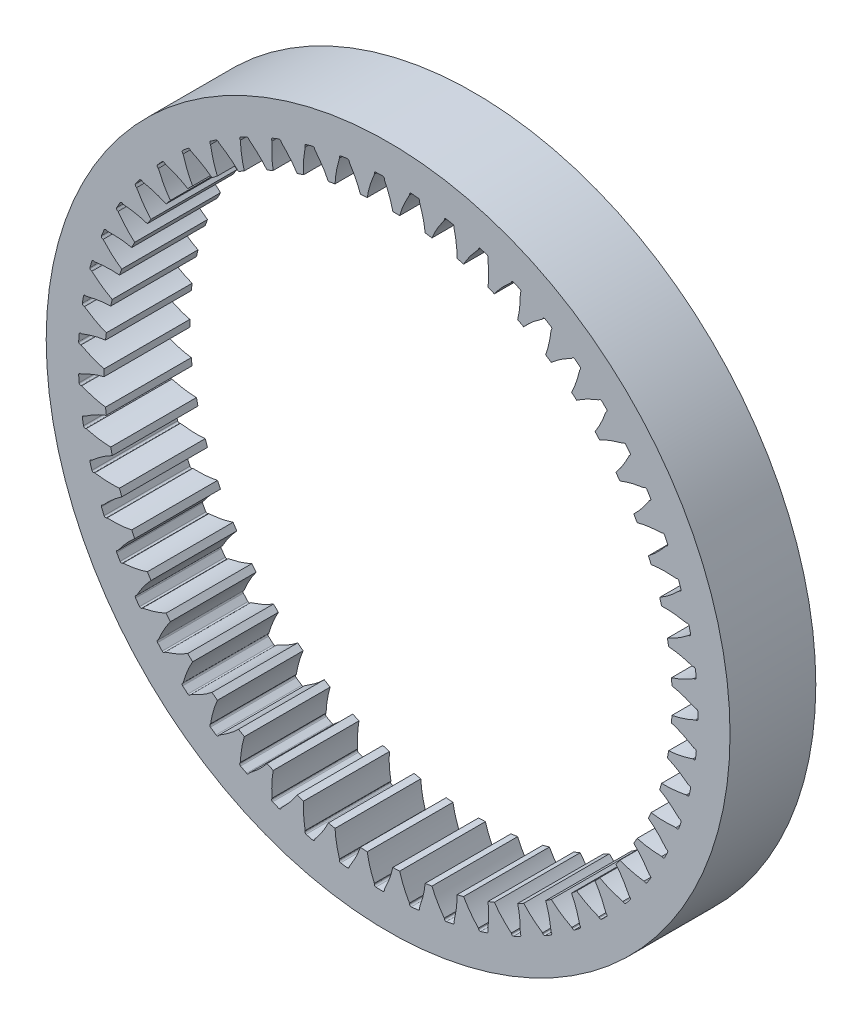
SolidWorks part; units mm, degrees
ref_plane "Front Plane" through (0, 0, 0) normal (0, 0, 1) x (1, 0, 0)
ref_plane "Top Plane" through (0, 0, 0) normal (0, 1, 0) x (1, 0, 0)
ref_plane "Right Plane" through (0, 0, 0) normal (1, 0, 0) x (0, 0, -1)
ref_axis "Gear Axis" through (0, 0, -0.5001) along (0, 0, 1)
sketch "Blank Sketch" plane through (0, 0, 0) normal (0, 0, 1) x (1, 0, 0)
  circle A0 centre (0, 0) radius 39.875
  circle A1 centre (0, 0) radius 33.125
  dimension "Rim" = 79.75
  dimension "Tip" = 66.25
extrude "Blank" add sketch "Blank Sketch" along normal blind 10
sketch "Tooth Space Sketch" plane through (0, 0, 0) normal (0, 0, 1) x (1, 0, 0)
  line L0 (32.4618, 1.5746) -> (31.8376, 1.5443)
  line L1 (32.4618, -1.5746) -> (31.8376, -1.5443)
  line L2 (31.8376, 1.5443) -> (31.8376, -1.5443)
  line L3 (35.839, 0.5828) -> (35.9323, 0.5843)
  line L4 (35.839, -0.5828) -> (35.9323, -0.5843)
  circle A0 centre (0, 0) radius 31.875 construction
  arc A1 (36.1228, 0.3989) -> (35.9323, 0.5843) centre (35.9353, 0.3968) ccw
  arc A2 (35.9323, -0.5843) -> (36.1228, -0.3989) centre (35.9353, -0.3968) ccw
  arc A3 (36.1228, -0.3989) -> (36.1228, 0.3989) centre (0, 0) ccw
  spline S0 degree 4 poles (32.3488, 1.5797) (32.3794, 1.5788) (32.4354, 1.5763) (32.4783, 1.5738) (32.5874, 1.5653) (32.6703, 1.5565) (32.7761, 1.5441) (32.8818, 1.5291) (32.9919, 1.512) (33.099, 1.4933) (33.2074, 1.4728) (33.3145, 1.451) (33.422, 1.4276) (33.5522, 1.3976) (33.7092, 1.3587) (33.8908, 1.3104) (34.0997, 1.2498) (34.3075, 1.1855) (34.5185, 1.1151) (34.721, 1.0444) (34.934, 0.9647) (35.1265, 0.8904) (35.3493, 0.7984) (35.5186, 0.7274) (35.7608, 0.619) (35.8709, 0.5684) (36.0228, 0.4968) (36.0994, 0.4599) (36.1385, 0.4409) (36.1582, 0.4312) knots 0 0 0 0 0 0.027604 0.045881 0.064918 0.092335 0.119753 0.14717 0.174587 0.202005 0.229422 0.256839 0.284256 0.311674 0.363255 0.418089 0.472924 0.527758 0.582593 0.637427 0.692262 0.747097 0.801931 0.856766 0.9116 0.9558 0.9779 1 1 1 1 1 construction
  spline S1 degree 4 poles (32.4618, 1.5746) (32.478, 1.5736) (32.5109, 1.5713) (32.5874, 1.5653) (32.6703, 1.5565) (32.7761, 1.5441) (32.8818, 1.5291) (32.9919, 1.512) (33.099, 1.4933) (33.2074, 1.4728) (33.3145, 1.451) (33.422, 1.4276) (33.5522, 1.3976) (33.7092, 1.3587) (33.8908, 1.3104) (34.0997, 1.2498) (34.3075, 1.1855) (34.5185, 1.1151) (34.721, 1.0444) (34.934, 0.9647) (35.1265, 0.8904) (35.3493, 0.7984) (35.5186, 0.7274) (35.7095, 0.6419) (35.795, 0.6031) (35.839, 0.5828) knots 0.027604 0.027604 0.027604 0.027604 0.027604 0.045881 0.064918 0.092335 0.119753 0.14717 0.174587 0.202005 0.229422 0.256839 0.284256 0.311674 0.363255 0.418089 0.472924 0.527758 0.582593 0.637427 0.692262 0.747097 0.801931 0.856766 0.9116 0.9116 0.9116 0.9116 0.9116
  spline S2 degree 4 poles (32.3488, -1.5797) (32.3794, -1.5788) (32.4354, -1.5763) (32.4783, -1.5738) (32.5874, -1.5653) (32.6703, -1.5565) (32.7761, -1.5441) (32.8818, -1.5291) (32.9919, -1.512) (33.099, -1.4933) (33.2074, -1.4728) (33.3145, -1.451) (33.422, -1.4276) (33.5522, -1.3976) (33.7092, -1.3587) (33.8908, -1.3104) (34.0997, -1.2498) (34.3075, -1.1855) (34.5185, -1.1151) (34.721, -1.0444) (34.934, -0.9647) (35.1265, -0.8904) (35.3493, -0.7984) (35.5186, -0.7274) (35.7608, -0.619) (35.8709, -0.5684) (36.0228, -0.4968) (36.0994, -0.4599) (36.1385, -0.4409) (36.1582, -0.4312) knots 0 0 0 0 0 0.027604 0.045881 0.064918 0.092335 0.119753 0.14717 0.174587 0.202005 0.229422 0.256839 0.284256 0.311674 0.363255 0.418089 0.472924 0.527758 0.582593 0.637427 0.692262 0.747097 0.801931 0.856766 0.9116 0.9558 0.9779 1 1 1 1 1 construction
  spline S3 degree 4 poles (32.4618, -1.5746) (32.478, -1.5736) (32.5109, -1.5713) (32.5874, -1.5653) (32.6703, -1.5565) (32.7761, -1.5441) (32.8818, -1.5291) (32.9919, -1.512) (33.099, -1.4933) (33.2074, -1.4728) (33.3145, -1.451) (33.422, -1.4276) (33.5522, -1.3976) (33.7092, -1.3587) (33.8908, -1.3104) (34.0997, -1.2498) (34.3075, -1.1855) (34.5185, -1.1151) (34.721, -1.0444) (34.934, -0.9647) (35.1265, -0.8904) (35.3493, -0.7984) (35.5186, -0.7274) (35.7095, -0.6419) (35.795, -0.6031) (35.839, -0.5828) knots 0.027604 0.027604 0.027604 0.027604 0.027604 0.045881 0.064918 0.092335 0.119753 0.14717 0.174587 0.202005 0.229422 0.256839 0.284256 0.311674 0.363255 0.418089 0.472924 0.527758 0.582593 0.637427 0.692262 0.747097 0.801931 0.856766 0.9116 0.9116 0.9116 0.9116 0.9116
  dimension "Root" = 36.125
  dimension "Fillet" = 0.1875
  dimension "Cap" = 63.75
extrude "Tooth Space" cut sketch "Tooth Space Sketch" against normal through all both and the other way through all both
pattern_circular "Teeth" count 55 over 360 about axis through (0, 0, -0.5001) along (0, 0, 1) of "Tooth Space"
equation "\"No. of Teeth\"= 55"
equation "\"Module\"= 1.25"
equation "\"Pressure Angle\"= 20"
equation "\"Inner Diameter\"= ( \"No. of Teeth\" - 2 ) * \"Module\""
equation "\"Pitch Diameter\"= \"No. of Teeth\" * \"Module\""
equation "\"Backlash\"= 0.3 * \"Module\""
equation "\"Arc Length\"= ( ( \"Module\" * pi ) / 2 + \"Backlash\" )"
equation "\"Fillet Radius\"= 0.15 * \"Module\""
equation "\"Tooth Depth\"= IIF ( \"Module\" <= 1.25 , \"Module\" * 2.4 , \"Module\" * 2.25 )"
equation "\"Face Width\"= 10"
equation "\"Root Diameter\"= \"Inner Diameter\" + 2 * \"Tooth Depth\""
equation "\"Rim Diameter\"= \"Root Diameter\" + 6 * \"Module\""
equation "\"Base Diameter\"= \"Pitch Diameter\" * cos ( \"Pressure Angle\" )"
equation "\"Base Radius\"= \"Base Diameter\" / 2"
equation "\"Tooth Thickness\"= \"Module\" * pi - \"Arc Length\""
equation "\"Half Space Angle\"= ( \"Arc Length\" / \"Pitch Diameter\" ) * 180 / pi"
equation "\"Involute Fn\"= tan ( \"Pressure Angle\" ) - \"Pressure Angle\" * pi / 180"
equation "\"Flank Offset\"= 0 - \"Arc Length\" / \"Pitch Diameter\" - \"Involute Fn\""
equation "\"Tip Cap Diameter\"= \"Inner Diameter\" - 2 * \"Module\""
equation "\"Flank Start Diameter\"= IIF ( \"Base Diameter\" >= ( \"Inner Diameter\" - \"Module\" ) , \"Base Diameter\" , \"Inner Diameter\" - \"Module\" )"
equation "\"Flank End Diameter\"= \"Root Diameter\" - 3 * \"Fillet Radius\""
equation "\"Involute t1\"= ( abs ( ( \"Flank Start Diameter\" / \"Base Diameter\" ) ^ 2 - 1 ) ) ^ 0.5"
equation "\"Involute t2\"= ( abs ( ( \"Flank End Diameter\" / \"Base Diameter\" ) ^ 2 - 1 ) ) ^ 0.5"
equation "\"Flank Arc Radius\"= ( \"Pitch Diameter\" / 2 ) * sin ( \"Pressure Angle\" )"
equation "\"Flank Centre Angle\"= \"Half Space Angle\" - \"Pressure Angle\""
equation "\"Rim@Blank Sketch\"= \"Rim Diameter\""
equation "\"Tip@Blank Sketch\"= \"Inner Diameter\""
equation "\"Width@Blank\"= \"Face Width\""
equation "\"Root@Tooth Space Sketch\"= \"Root Diameter\" / 2"
equation "\"Fillet@Tooth Space Sketch\"= \"Fillet Radius\""
equation "\"Cap@Tooth Space Sketch\"= \"Tip Cap Diameter\""
equation "\"Count@Teeth\"= \"No. of Teeth\""
